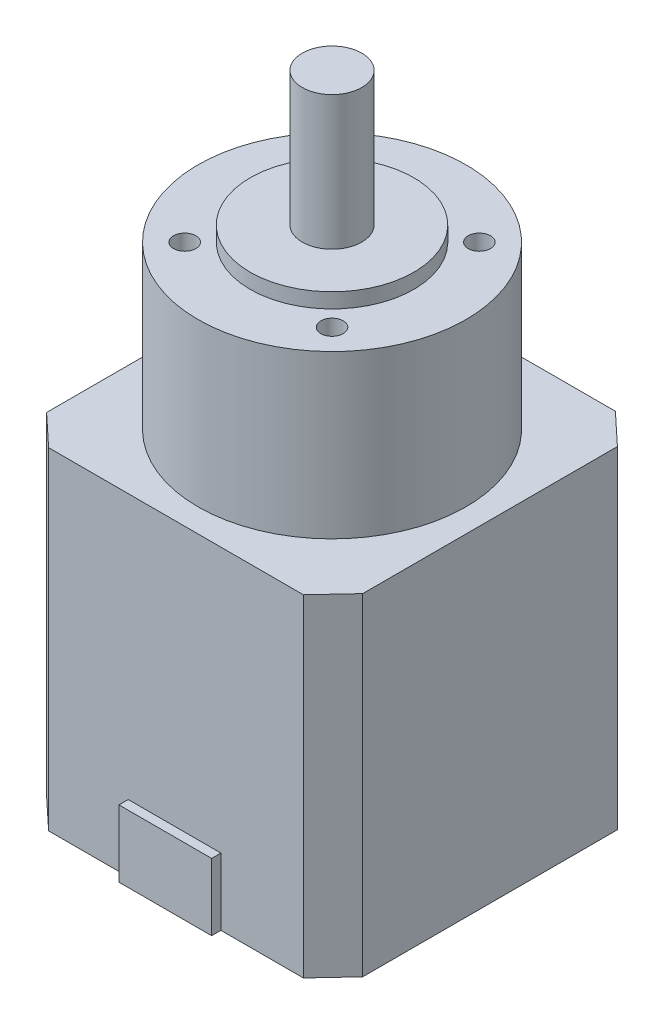
SolidWorks part; units mm, degrees
material "AISI 1015 Steel, Cold Drawn (SS)"
ref_plane "Front Plane" through (0, 0, 0) normal (0, 0, 1) x (1, 0, 0)
ref_plane "Top Plane" through (0, 0, 0) normal (0, 1, 0) x (1, 0, 0)
ref_plane "Right Plane" through (0, 0, 0) normal (1, 0, 0) x (0, 0, -1)
sketch "Sketch1" plane through (0, 0, 0) normal (0, 1, 0) x (1, 0, 0)
  line L0 (-21.16, 16.7988) -> (-17.0846, 21.16)
  line L1 (-21.16, 21.16) -> (21.16, 21.16)
  line L2 (-21.16, 21.16) -> (-21.16, -21.16)
  line L3 (-21.16, -21.16) -> (21.16, -21.16)
  line L4 (21.16, 21.16) -> (21.16, -21.16)
  line L5 (-21.16, 21.16) -> (21.16, -21.16) construction
  line L6 (-21.16, -21.16) -> (21.16, 21.16) construction
  line L7 (16.9154, 21.16) -> (21.2766, 17.0846)
  line L8 (21.2766, -16.9154) -> (17.2012, -21.2766)
  line L9 (-16.7988, -21.2766) -> (-21.16, -17.2012)
  line L12 (-6.2297, -21.16) -> (-6.2297, -22.4053)
  line L13 (-6.2297, -22.4053) -> (6.2297, -22.4053)
  line L14 (6.2297, -21.16) -> (6.2297, -22.4053)
  line L15 (0, -21.16) -> (6.2297, -22.4053) construction
  line L16 (-6.2297, -22.4053) -> (0, -21.16) construction
  circle A0 centre (0, 0) radius 18.01
  circle A1 centre (0, 0) radius 14 construction
  circle A2 centre (9.8995, 9.8995) radius 1.5
  circle A3 centre (9.8995, -9.8995) radius 1.5
  circle A4 centre (-9.8995, -9.8995) radius 1.5
  circle A5 centre (-9.8995, 9.8995) radius 1.5
  circle A6 centre (0, 0) radius 11
  circle A7 centre (0, 0) radius 4
  point P0 (0, 0)
  point P13 (0, -21.16)
  point P22 (0.1166, 0)
  point P25 (0.1166, -0.1166)
  point P32 (0, 0)
  point P33 (0, -0.1166)
  dimension "D2" = 22
  dimension "D5" = 8
  dimension "D6" = 3
  dimension "D7" = 4
  dimension "D1" = 42.32
  dimension "D4" = 34
  dimension "D3" = 4
extrude "Boss-Extrude1" add sketch "Sketch1" along normal blind 44.6 contours L9 L3 L8 L4 L7 L1 L0 L2 A0 | A0 A6 A5 A4 A3 A2 | A6 A7 | A2 | A3 | A4 | A5 | A7 region at (-18.685, 0, -18.5708) region at (-17.5006, 0, 0) region at (9.8995, 0, -9.8995) region at (9.8995, 0, 9.8995) region at (-9.8995, 0, 9.8995) region at (-9.8995, 0, -9.8995) region at (-10.6889, 0, 0) region at (0, 0, 0)
extrude "Boss-Extrude2" add sketch "Sketch1<3>" along normal blind 21.8 from surface contours A0 A6 A5 A4 A3 A2 | A6 A7 | A4 | A3 | A2 | A5 | A7 region at (-17.5006, 0, 0) region at (9.8995, 0, -9.8995) region at (9.8995, 0, 9.8995) region at (-9.8995, 0, 9.8995) region at (-9.8995, 0, -9.8995) region at (-10.6889, 0, 0) region at (0, 0, 0) starting at face at (0.0272, 44.6, 0.0311)
sketch "Sketch1<3>" plane through (0, 0, 0) normal (0, 1, 0) x (1, 0, 0) same geometry as "Sketch1"
extrude "Boss-Extrude3" add sketch "Sketch1<4>" along normal blind 2 from surface contours A6 A7 | A7 region at (-10.6889, 0, 0) region at (0, 0, 0) starting at face at (0, 66.4, 18.01)
sketch "Sketch1<4>" plane through (0, 0, 0) normal (0, 1, 0) x (1, 0, 0) same geometry as "Sketch1"
extrude "Cut-Extrude1" cut sketch "Sketch1<5>" against normal blind 4.5 from surface contours A3 | A2 | A5 | A4 region at (9.8995, 0, -9.8995) region at (9.8995, 0, 9.8995) region at (-9.8995, 0, 9.8995) region at (-9.8995, 0, -9.8995) starting at face at (0, 66.4, 11)
sketch "Sketch1<5>" plane through (0, 0, 0) normal (0, 1, 0) x (1, 0, 0) same geometry as "Sketch1"
extrude "Boss-Extrude4" add sketch "Sketch1<6>" along normal blind 20 from surface contours A7 region at (0, 0, 0) starting at face at (-9.8995, 66.4, 11.3995)
sketch "Sketch1<6>" plane through (0, 0, 0) normal (0, 1, 0) x (1, 0, 0) same geometry as "Sketch1"
extrude "Boss-Extrude5" add sketch "Sketch1<7>" along normal blind 9 contours L14 L3 L12 L13 region at (0, 0, 21.7826)
sketch "Sketch1<7>" plane through (0, 0, 0) normal (0, 1, 0) x (1, 0, 0) same geometry as "Sketch1"
